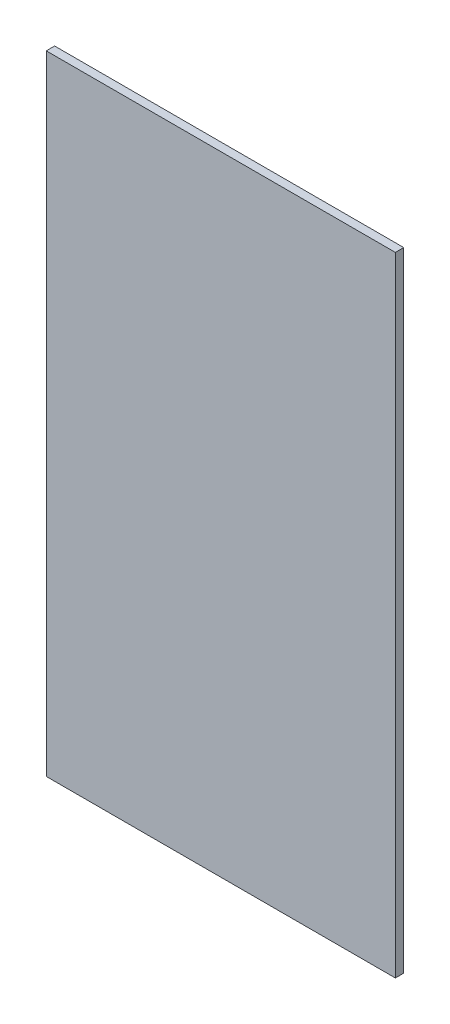
SolidWorks part; units mm, degrees
ref_plane "Ebene vorne" through (0, 0, 0) normal (0, 0, 1) x (1, 0, 0)
ref_plane "Ebene oben" through (0, 0, 0) normal (0, 1, 0) x (1, 0, 0)
ref_plane "Ebene rechts" through (0, 0, 0) normal (1, 0, 0) x (0, 0, -1)
sketch "DimensionsSketch" plane through (0, 0, 0) normal (0, 0, 1) x (1, 0, 0)
  line L1 (-125, -225) -> (125, -225)
  line L2 (-125, -225) -> (-125, 225)
  line L3 (-125, 225) -> (125, 225)
  line L4 (125, -225) -> (125, 225)
  line L5 (-125, -225) -> (125, 225) construction
  line L6 (-125, 225) -> (125, -225) construction
  point P0 (0, 0)
  dimension "D1" = 250
  dimension "D2" = 450
extrude "Dimensions" add sketch "DimensionsSketch" along normal mid plane 6
sketch "Sketch1" [suppressed] plane through (0, -225, 0) normal (0, -1, 0) x (1, 0, 0)
  line L4 (132, -20) -> (132, 20)
  line L5 (132, 20) -> (112, 0)
  line L6 (112, 0) -> (132, -20)
  line L7 (125, 0) -> (132, 0) construction
  line L8 (125, 3) -> (125, -3) construction
  dimension "D1" = 7
  dimension "D2" = 90
  dimension "D3" = 40
extrude "Boss-Extrude1" [suppressed] add sketch "Sketch1" against normal offset from surface (464 mm away) 7 from offset 7 offset beyond the face yes
sketch "Sketch2" [suppressed] plane through (-125, 0, 0) normal (-1, 0, 0) x (0, 0, 1)
  line L0 (-20, -232) -> (20, -232)
  line L1 (20, -232) -> (0, -212)
  line L2 (0, -212) -> (-20, -232)
  dimension "D1" = 90
extrude "Boss-Extrude2" [suppressed] add sketch "Sketch2" against normal up to surface (264 mm away) from offset 7
mirror "Mirror1" [suppressed] about plane through (0, 0, 0) normal (1, 0, 0)
mirror "Mirror2" [suppressed] about plane through (0, 0, 0) normal (0, 1, 0)
